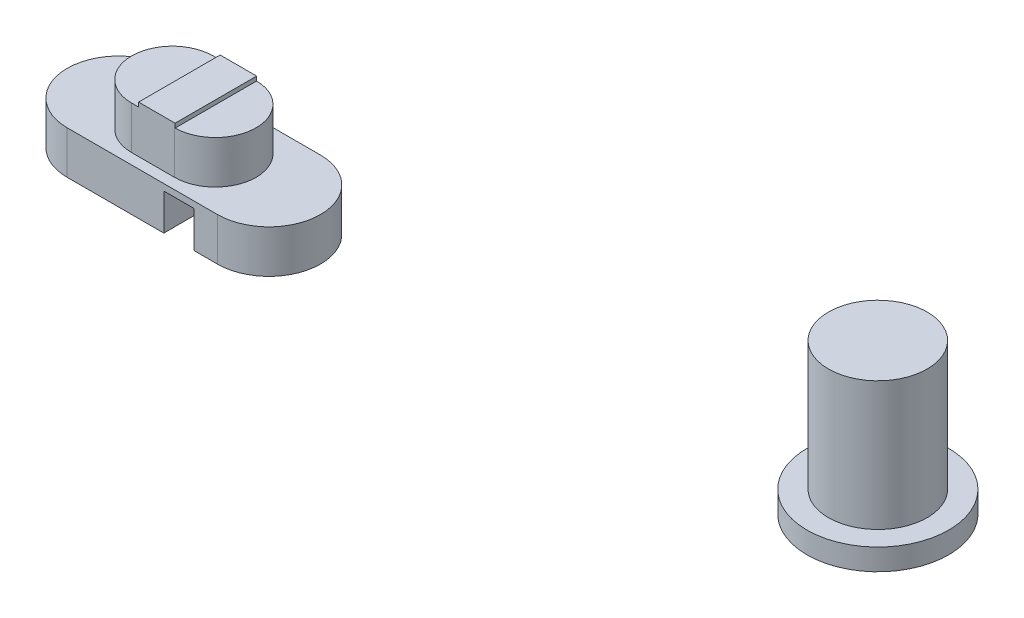
SolidWorks part; units mm, degrees
ref_plane "前视" through (0, 0, 0) normal (0, 0, 1) x (1, 0, 0)
ref_plane "上视" through (0, 0, 0) normal (0, 1, 0) x (1, 0, 0)
ref_plane "右视" through (0, 0, 0) normal (1, 0, 0) x (0, 0, -1)
sketch "草图1" plane through (0, 0, 0) normal (0, 1, 0) x (1, 0, 0)
  line L0 (-33.4642, 0.5) -> (-26.4642, 0.5)
  line L1 (-33.4642, -4.3) -> (-26.4642, -4.3)
  line L2 (-38.1105, -1.9) -> (-21.8178, -1.9) construction
  line L3 (-29.9642, -1.9) -> (-29.9642, 3.5935) construction
  line L4 (-30.9642, 0) -> (-28.9642, 0)
  line L5 (-30.9642, -3.8) -> (-28.9642, -3.8)
  circle A0 centre (0, 0) radius 2.3
  circle A1 centre (0, 0) radius 3.3
  arc A2 (-26.4642, 0.5) -> (-26.4642, -4.3) centre (-26.4642, -1.9) cw
  arc A3 (-33.4642, -4.3) -> (-33.4642, 0.5) centre (-33.4642, -1.9) cw
  arc A4 (-28.9642, 0) -> (-28.9642, -3.8) centre (-28.9642, -1.9) cw
  arc A5 (-30.9642, 0) -> (-30.9642, -3.8) centre (-30.9642, -1.9) ccw
  point P19 (-29.9642, -3.8)
  point P20 (-29.9642, 0)
  dimension "D1" = 4.6
  dimension "D2" = 1
  dimension "D3" = 7
  dimension "D5" = 3.8
  dimension "D4" = 4.8
  dimension "D6" = 2
extrude "凸台-拉伸1" add sketch "草图1" against normal blind 1 contours A1 A0 | A0 region at (0, 0, 0) region at (-3.2067, 0, 0)
extrude "凸台-拉伸2" add sketch "草图1<3>" along normal blind 6 contours A0 region at (0, 0, 0)
sketch "草图1<3>" plane through (0, 0, 0) normal (0, 1, 0) x (1, 0, 0) same geometry as "草图1"
extrude "凸台-拉伸3" add sketch "草图1<5>" against normal blind 2 separate body contours A3 L1 A2 L0 | L4 A5 L5 A4 region at (-29.9642, 0, -0.3726) region at (-29.9642, 0, 1.9)
sketch "草图1<5>" plane through (0, 0, 0) normal (0, 1, 0) x (1, 0, 0) same geometry as "草图1"
extrude "凸台-拉伸4" add sketch "草图1<6>" along normal blind 2 contours L4 A5 L5 A4 region at (-29.9642, 0, 1.9)
sketch "草图1<6>" plane through (0, 0, 0) normal (0, 1, 0) x (1, 0, 0) same geometry as "草图1"
sketch "草图2" plane through (0, 0, -0.5) normal (0, 0, -1) x (-1, 0, 0)
  line L0 (33.4642, -2) -> (26.4642, -2) construction
  line L1 (28.9642, -2) -> (27.5642, -2)
  line L2 (28.9642, -2) -> (28.9642, -0.3)
  line L3 (28.9642, -0.3) -> (27.5642, -0.3)
  line L4 (27.5642, -2) -> (27.5642, -0.3)
  line L5 (24.0642, 0) -> (24.0642, -2) construction
  dimension "D1" = 1.7
  dimension "D2" = 1.4
  dimension "D3" = 3.5
extrude "切除-拉伸1" cut sketch "草图2" against normal through all
sketch "草图3" plane through (0, 2, 0) normal (0, 1, 0) x (1, 0, 0)
  line L0 (-30.9642, 0) -> (-28.9642, 0) construction
  line L1 (-28.9382, 0) -> (-30.6387, 0)
  line L2 (-28.9382, 0) -> (-28.9382, -3.8)
  line L3 (-28.9382, -3.8) -> (-30.6387, -3.8)
  line L4 (-30.6387, 0) -> (-30.6387, -3.8)
  line L5 (-30.9642, -3.8) -> (-28.9642, -3.8) construction
  line L6 (-29.7884, 0) -> (-29.7884, -3.8) construction
extrude "凸台-拉伸5" add sketch "草图3" along normal blind 0.2
